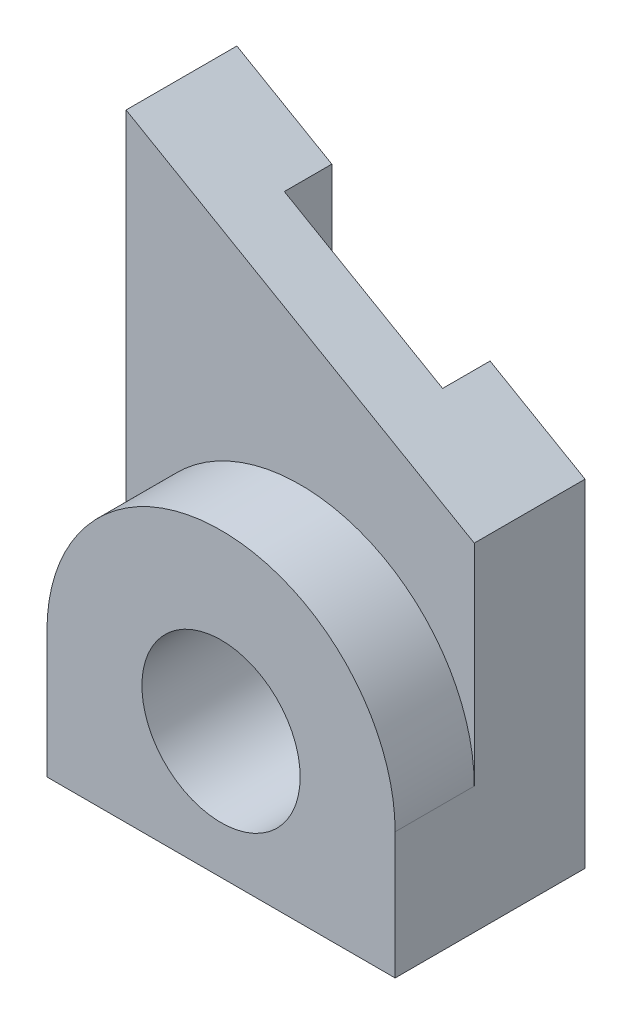
SolidWorks part; units mm, degrees
ref_plane "Front Plane" through (0, 0, 0) normal (0, 0, 1) x (1, 0, 0)
ref_plane "Top Plane" through (0, 0, 0) normal (0, 1, 0) x (1, 0, 0)
ref_plane "Right Plane" through (0, 0, 0) normal (1, 0, 0) x (0, 0, -1)
sketch "Sketch1" plane through (0, 0, 0) normal (0, 0, 1) x (1, 0, 0)
  line L0 (-22, -16) -> (22, -16)
  line L1 (22, -16) -> (22, 26.5966)
  line L2 (22, 26.5966) -> (-22, 52)
  line L3 (-22, 52) -> (-22, -16)
  line L4 (-45.0201, 0) -> (45.0201, 0) construction
  circle A0 centre (0, 0) radius 10
  arc A1 (-22, 0) -> (22, 0) centre (0, 0) cw
  point P9 (0, 0)
  point P10 (0, 0)
  point P14 (0, 0)
  dimension "D4" = 20
  dimension "D1" = 16
  dimension "D2" = 68
  dimension "D3" = 60
  dimension "D5" = 44
extrude "Boss-Extrude1" add sketch "Sketch1" along normal blind 10 contours A1 L4 A0 | L4 L3 L0 L1 A0 region at (-21.5318, -8, 0) region at (0, 10.6634, 0)
extrude "Boss-Extrude2" add sketch "Sketch1<3>" against normal blind 14 contours L3 A1 L1 L2 | A1 L4 A0 | L4 L3 L0 L1 A0 region at (-21.5318, -8, 0) region at (0, 10.6634, 0) region at (-4.2301, 28.9622, 0)
sketch "Sketch1<3>" plane through (0, 0, 0) normal (0, 0, 1) x (1, 0, 0) same geometry as "Sketch1"
sketch "Sketch3" plane through (0, -16, 0) normal (0, -1, 0) x (1, 0, 0)
  line L0 (0, -19.123) -> (0, 19.123) construction
  line L1 (-10, -14) -> (-10, -8)
  line L2 (-22, -14) -> (22, -14) construction
  line L3 (-10, -8) -> (10, -8)
  line L4 (10, -8) -> (10, -14)
  line L5 (-10, -14) -> (10, -14)
  point P4 (0, 0)
  dimension "D1" = 20
  dimension "D2" = 6
extrude "Cut-Extrude2" cut sketch "Sketch3" against normal through all
